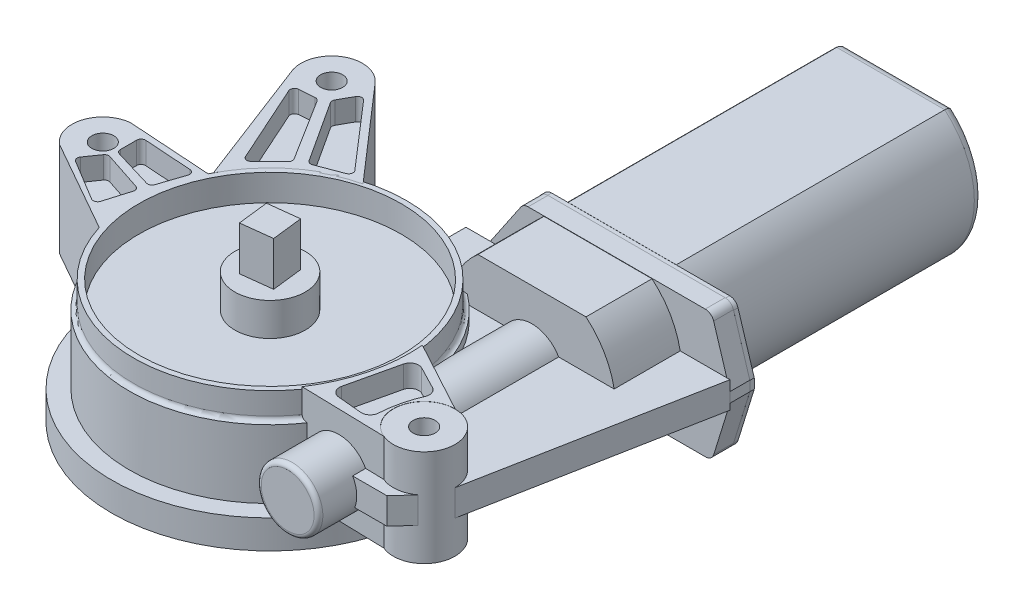
SolidWorks part; units mm, degrees
ref_plane "Спереди" through (0, 0, 0) normal (0, 0, 1) x (1, 0, 0)
ref_plane "Сверху" through (0, 0, 0) normal (0, 1, 0) x (1, 0, 0)
ref_plane "Справа" through (0, 0, 0) normal (1, 0, 0) x (0, 0, -1)
sketch "Эскиз3" plane through (0, 0, 0) normal (0, 0, 1) x (1, 0, 0)
  line L0 (0, 0) -> (56.6194, 0) construction
  line L1 (-12.278, 14.5) -> (12.278, 14.5)
  line L2 (-12.278, -14.5) -> (12.278, -14.5)
  arc A0 (-12.278, 14.5) -> (-12.278, -14.5) centre (0, 0) ccw
  arc A1 (12.278, -14.5) -> (12.278, 14.5) centre (0, 0) ccw
  dimension "D1" = 14.5
extrude "Вытянуть1" add sketch "Эскиз3" along normal blind 63
sketch "Эскиз4" plane through (0, 0, 0) normal (0, 0, -1) x (-1, 0, 0)
  circle A0 centre (0, 0) radius 6.75
extrude "Вытянуть2" add sketch "Эскиз4" along normal blind 5
sketch "Эскиз5" plane through (0, 0, -5) normal (0, 0, -1) x (-1, 0, 0)
  circle A0 centre (0, 0) radius 2.5
extrude "Вытянуть3" add sketch "Эскиз5" along normal blind 2 draft 33
sketch "Эскиз7" plane through (0, 0, 63) normal (0, 0, 1) x (1, 0, 0)
  line L0 (-29.9997, -12.4725) -> (-29.9997, -5.3043)
  line L1 (29.9997, -1.118) -> (26.3061, -13.0633)
  line L2 (-17.7001, 13.5889) -> (-29.6591, -4.1879)
  line L3 (29.9997, -1.118) -> (29.9997, 1.118)
  line L4 (24.3954, 14.4725) -> (-16.0407, 14.4725)
  line L5 (29.9997, 1.118) -> (26.3061, 13.0633)
  line L6 (24.3954, -14.4725) -> (-27.9997, -14.4725)
  line L7 (-29.9997, 0) -> (-36.554, 0) construction
  line L10 (0, 0) -> (0, 25.9429) construction
  arc A0 (-27.9997, -14.4725) -> (-29.9997, -12.4725) centre (-27.9997, -12.4725) cw
  arc A1 (-29.6591, -4.1879) -> (-29.9997, -5.3043) centre (-27.9997, -5.3043) ccw
  arc A5 (24.3954, -14.4725) -> (26.3061, -13.0633) centre (24.3954, -12.4725) ccw
  arc A6 (24.3954, 14.4725) -> (26.3061, 13.0633) centre (24.3954, 12.4725) cw
  arc A7 (-17.7001, 13.5889) -> (-16.0407, 14.4725) centre (-16.0407, 12.4725) cw
  point P0 (0, 0)
extrude "Вытянуть4" add sketch "Эскиз7" along normal blind 1
ref_plane "Плоскость1" through (0, -16.5, 0) normal (0, -1, 0) x (1, 0, 0)
sketch "Эскиз8" plane through (0, -16.5, 0) normal (0, -1, 0) x (1, 0, 0)
  line L0 (0, 0) -> (0, 81.1276) construction
  line L1 (23.2237, 64) -> (84.0137, 64) construction
  circle A1 centre (-34, 109) radius 36
extrude "Вытянуть5" add sketch "Эскиз8" against normal blind 6.5 separate body
sketch "Эскиз10" plane through (0, -10, 0) normal (0, -1, 0) x (-1, 0, 0)
  line L0 (0, 0) -> (0, 13.3727) construction
  circle A1 centre (34, -109) radius 32
extrude "Вытянуть6" add sketch "Эскиз10" against normal blind 15.5
sketch "Эскиз11" plane through (0, 5.5, 0) normal (0, 1, 0) x (1, 0, 0)
  line L0 (0, 0) -> (0, -27.8136) construction
  circle A2 centre (-34, -109) radius 29.8
  circle A3 centre (-34, -109) radius 31
extrude "Вытянуть7" add sketch "Эскиз11" along normal blind 6
fillet "Скругление1" radius 1 1 edges at (-34, 5.5, 78)
sketch "Эскиз12" plane through (0, -16.5, 0) normal (0, 1, 0) x (-1, 0, 0)
  line L0 (0, 0) -> (0, 26.2402) construction
  line L1 (65.6508, 115.1062) -> (55.1135, 133.3573)
  line L20 (51.6523, 133.3622) -> (41.0102, 115.0506)
  line L21 (63.9244, 112.1062) -> (42.7451, 112.0457)
  line L22 (55.1135, 84.6427) -> (65.6508, 102.8938)
  line L23 (63.9244, 105.8938) -> (42.7451, 105.9543)
  line L24 (51.6523, 84.6378) -> (41.0102, 102.9494)
  line L25 (23.4628, 78.5365) -> (44.5372, 78.5365)
  line L26 (46.2722, 81.5316) -> (35.7349, 99.9037)
  line L27 (21.7278, 81.5316) -> (32.2651, 99.9037)
  line L28 (2.3492, 102.8938) -> (12.8865, 84.6427)
  line L29 (16.3477, 84.6378) -> (26.9898, 102.9494)
  line L30 (4.0756, 105.8938) -> (25.2549, 105.9543)
  line L31 (12.8865, 133.3573) -> (2.3492, 115.1062)
  line L32 (4.0756, 112.1062) -> (25.2549, 112.0457)
  line L33 (16.3477, 133.3622) -> (26.9898, 115.0506)
  line L34 (46.2722, 136.4684) -> (35.7349, 118.0963)
  line L35 (21.7278, 136.4684) -> (32.2651, 118.0963)
  line L36 (44.5372, 139.4635) -> (23.4628, 139.4635)
  arc A18 (63.9244, 112.1062) -> (65.6508, 115.1062) centre (63.9187, 114.1062) ccw
  arc A19 (55.1135, 133.3573) -> (51.6523, 133.3622) centre (53.3815, 132.3573) ccw
  arc A20 (41.0102, 115.0506) -> (42.7451, 112.0457) centre (42.7394, 114.0457) ccw
  arc A21 (51.6523, 84.6378) -> (55.1135, 84.6427) centre (53.3815, 85.6427) ccw
  arc A22 (65.6508, 102.8938) -> (63.9244, 105.8938) centre (63.9187, 103.8938) ccw
  arc A23 (42.7451, 105.9543) -> (41.0102, 102.9494) centre (42.7394, 103.9543) ccw
  arc A24 (21.7278, 81.5316) -> (23.4628, 78.5365) centre (23.4628, 80.5365) ccw
  arc A25 (44.5372, 78.5365) -> (46.2722, 81.5316) centre (44.5372, 80.5365) ccw
  arc A26 (35.7349, 99.9037) -> (32.2651, 99.9037) centre (34, 98.9086) ccw
  arc A27 (4.0756, 105.8938) -> (2.3492, 102.8938) centre (4.0813, 103.8938) ccw
  arc A28 (12.8865, 84.6427) -> (16.3477, 84.6378) centre (14.6185, 85.6427) ccw
  arc A29 (26.9898, 102.9494) -> (25.2549, 105.9543) centre (25.2606, 103.9543) ccw
  arc A30 (16.3477, 133.3622) -> (12.8865, 133.3573) centre (14.6185, 132.3573) ccw
  arc A31 (2.3492, 115.1062) -> (4.0756, 112.1062) centre (4.0813, 114.1062) ccw
  arc A32 (25.2549, 112.0457) -> (26.9898, 115.0506) centre (25.2606, 114.0457) ccw
  arc A33 (32.2651, 118.0963) -> (35.7349, 118.0963) centre (34, 119.0914) ccw
  arc A34 (46.2722, 136.4684) -> (44.5372, 139.4635) centre (44.5372, 137.4635) ccw
  arc A35 (23.4628, 139.4635) -> (21.7278, 136.4684) centre (23.4628, 137.4635) ccw
  point P113 (34, 115.0714)
  point P114 (47.9899, 139.4635)
  point P115 (20.0101, 139.4635)
extrude "Вытянуть8" cut sketch "Эскиз12" along normal blind 1.2
sketch "Эскиз13" plane through (0, 5.5, 0) normal (0, 1, 0) x (1, 0, 0)
  line L0 (0, 0) -> (0, 38.3637) construction
  circle A1 centre (-34, -109) radius 8
extrude "Вытянуть9" add sketch "Эскиз13" along normal blind 7.5
sketch "Эскиз14" plane through (0, 13, 0) normal (0, 1, 0) x (1, 0, 0)
  line L0 (0, 0) -> (0, 36.0336) construction
  line L5 (-37.8867, -105.9351) -> (-30.9351, -105.1133)
  line L6 (-37.0649, -112.8867) -> (-37.8867, -105.9351)
  line L7 (-30.1133, -112.0649) -> (-37.0649, -112.8867)
  line L8 (-30.9351, -105.1133) -> (-30.1133, -112.0649)
  circle A1 centre (-34, -109) radius 3.5 construction
extrude "Вытянуть10" add sketch "Эскиз14" along normal blind 10
sketch "Эскиз15" plane through (0, 0, 64) normal (0, 0, 1) x (1, 0, 0)
  circle A0 centre (0, 0) radius 7
extrude "Вытянуть11" add sketch "Эскиз15" along normal blind 75
sketch "Эскиз16" plane through (0, 0, 64) normal (0, 0, 1) x (1, 0, 0)
  line L0 (12.278, 14.5) -> (-12.278, 14.5)
  line L1 (12.278, 14.5) -> (-12.278, 14.5) construction
  line L2 (12.278, -14.5) -> (-12.278, -14.5)
  arc A0 (-12.278, 14.5) -> (-12.278, -14.5) centre (0, 0) ccw
  arc A1 (12.278, -14.5) -> (12.278, 14.5) centre (0, 0) ccw
extrude "Вытянуть12" add sketch "Эскиз16" along normal blind 19.5
sketch "Эскиз17" plane through (0, 0, 64) normal (0, 0, 1) x (1, 0, 0)
  line L0 (-30.0005, -5.2705) -> (-30.0005, -12.4733)
  line L1 (29.9899, -1.1315) -> (26.3061, -13.0633)
  line L2 (24.361, 14.5741) -> (-15.8793, 14.5741)
  line L3 (29.9899, 1.1498) -> (29.9899, -1.1315)
  line L4 (-29.6549, -4.1467) -> (-17.5338, 13.6979)
  line L5 (0, 0) -> (0, 28.4439) construction
  line L6 (26.2716, 13.1654) -> (29.9899, 1.1498)
  line L7 (24.3951, -14.4733) -> (-28.0005, -14.4733)
  arc A0 (-28.0005, -14.4733) -> (-30.0005, -12.4733) centre (-28.0005, -12.4733) cw
  arc A1 (-29.6549, -4.1467) -> (-30.0005, -5.2705) centre (-28.0005, -5.2705) ccw
  arc A6 (26.3061, -13.0633) -> (24.3951, -14.4733) centre (24.3951, -12.4733) cw
  arc A7 (26.2716, 13.1654) -> (24.361, 14.5741) centre (24.361, 12.5741) ccw
  arc A8 (-15.8793, 14.5741) -> (-17.5338, 13.6979) centre (-15.8793, 12.5741) ccw
extrude "Вытянуть13" add sketch "Эскиз17" along normal blind 4.5
fillet "Скругление2" radius 1 1 edges at (7, 0, 139)
ref_plane "Плоскость2" through (0, -2.5, 0) normal (0, -1, 0) x (1, 0, 0)
ref_plane "Плоскость3" through (0, -10, 0) normal (0, 1, 0) x (-1, 0, 0)
sketch "Эскиз19" plane through (0, -10, 0) normal (0, 1, 0) x (-1, 0, 0)
  line L2 (0, 0) -> (0, -45.8668) construction
  circle A2 centre (-13, 121) radius 2.5
  circle A3 centre (-13, 121) radius 7
extrude "Вытянуть16" add sketch "Эскиз19" along normal blind 22
sketch "Эскиз18" plane through (0, -2.5, 0) normal (0, -1, 0) x (1, 0, 0)
  line L0 (-30.0005, 68.5) -> (29.9899, 68.5)
  line L1 (-2.1987, 112.5605) -> (-2.1987, 130.3043)
  line L2 (-2.1987, 130.3043) -> (13.853, 130.3043)
  line L3 (17.229, 126.5781) -> (13.853, 130.3043)
  line L4 (-30.0005, 77.2509) -> (-30.0005, 68.5)
  line L5 (29.9899, 68.5) -> (20, 121)
  line L6 (0, 0) -> (0, -15.0039) construction
  arc A1 (20, 121) -> (17.229, 126.5781) centre (13, 121) cw
  arc A3 (-30.0005, 77.2509) -> (-2.1987, 112.5605) centre (-34, 109) ccw
extrude "Вытянуть15" add sketch "Эскиз18" against normal blind 6
sketch "Эскиз20" plane through (0, -10, 0) normal (0, 1, 0) x (-1, 0, 0)
  line L2 (0, 0) -> (0, 43.7341) construction
  line L3 (-10.2818, 127.4507) -> (8.7473, 126.9805)
  line L4 (-13.0336, 113.982) -> (3.2391, 105.157)
  arc A9 (-13.0336, 113.982) -> (-10.2818, 127.4507) centre (-12.9558, 120.9816) ccw
  arc A10 (3.2391, 105.157) -> (8.7473, 126.9805) centre (37.2063, 108.1908) cw
extrude "Вытянуть21" add sketch "Эскиз20" along normal blind 22 separate body
sketch "Эскиз21" plane through (0, 12, 0) normal (0, 1, 0) x (1, 0, 0)
  line L3 (0, 0) -> (0, 31.3892) construction
  line L4 (-2.554, -124.8655) -> (2.9539, -125.3725)
  line L5 (-1.6954, -111.0431) -> (-4.3195, -122.4246)
  line L6 (6.2428, -112.3443) -> (1.1739, -109.7169)
  arc A5 (5.1338, -123.4968) -> (2.9539, -125.3725) centre (3.1372, -123.381) cw
  arc A6 (-2.554, -124.8655) -> (-4.3195, -122.4246) centre (-2.3706, -122.874) cw
  arc A7 (-1.6954, -111.0431) -> (1.1739, -109.7169) centre (0.2535, -111.4925) cw
  arc A8 (6.2428, -112.3443) -> (7.1603, -114.9089) centre (5.3224, -114.12) cw
  arc A9 (7.1603, -114.9089) -> (5.1338, -123.4968) centre (30.6107, -124.9754) ccw
extrude "Вытянуть23" cut sketch "Эскиз21" against normal blind 5
sketch "Эскиз22" plane through (0, -10, 0) normal (0, -1, 0) x (1, 0, 0)
  line L3 (0, 0) -> (0, 45.5523) construction
  line L4 (1.2936, 110.1573) -> (6.317, 112.4722)
  line L5 (-4.874, 122.5572) -> (-1.4559, 111.3884)
  line L6 (2.6512, 125.3994) -> (-3.0523, 125.1404)
  arc A5 (7.267, 115.1865) -> (6.317, 112.4722) centre (5.48, 114.2886) cw
  arc A6 (1.2936, 110.1573) -> (-1.4559, 111.3884) centre (0.4566, 111.9737) cw
  arc A7 (-4.874, 122.5572) -> (-3.0523, 125.1404) centre (-2.9616, 123.1425) cw
  arc A8 (2.6512, 125.3994) -> (4.728, 123.6372) centre (2.742, 123.4015) cw
  arc A9 (4.728, 123.6372) -> (7.267, 115.1865) centre (30.0699, 126.6445) ccw
extrude "Вытянуть24" cut sketch "Эскиз22" against normal blind 5
sketch "Эскиз23" plane through (0, -10, 0) normal (0, 1, 0) x (-1, 0, 0)
  line L0 (0, 0) -> (0, -17.6371) construction
  line L1 (72.3707, 65.9008) -> (61.3848, 94.4717)
  line L4 (60.6873, 58.442) -> (42.1989, 79.6831)
  arc A3 (42.1989, 79.6831) -> (61.3848, 94.4717) centre (35.4039, 108.3383) ccw
  circle A4 centre (66, 63) radius 2.5
  arc A6 (72.3707, 65.9008) -> (60.6873, 58.442) centre (66, 63) cw
extrude "Вытянуть27" add sketch "Эскиз23" along normal up to surface (21.5 mm away) separate body up to face at (-34, 11.5, 78)
sketch "Эскиз24" plane through (0, -10, 0) normal (0, 1, 0) x (1, 0, 0)
  line L0 (0, 0) -> (0, -33.9234) construction
  line L9 (-60.9369, -87.6399) -> (-68.9832, -69.7666)
  line L10 (-68.1428, -68.3587) -> (-64.6571, -68.1089)
  line L11 (-63.7383, -68.5752) -> (-54.9646, -82.5698)
  line L12 (-55.112, -83.8152) -> (-59.3252, -87.9437)
  line L13 (-51.701, -81.6376) -> (-46.1827, -79.5534)
  line L14 (-61.8946, -67.3981) -> (-52.8928, -81.2471)
  line L15 (-60.2372, -63.3116) -> (-61.9309, -66.3685)
  line L16 (-45.7799, -77.9636) -> (-58.6063, -63.1419)
  arc A9 (-68.1428, -68.3587) -> (-68.9832, -69.7666) centre (-68.0714, -69.3561) ccw
  arc A10 (-63.7383, -68.5752) -> (-64.6571, -68.1089) centre (-64.5856, -69.1064) ccw
  arc A11 (-55.112, -83.8152) -> (-54.9646, -82.5698) centre (-55.8119, -83.1009) ccw
  arc A12 (-60.9369, -87.6399) -> (-59.3252, -87.9437) centre (-60.0251, -87.2294) ccw
  arc A13 (-45.7799, -77.9636) -> (-46.1827, -79.5534) centre (-46.5361, -78.6179) cw
  arc A14 (-51.701, -81.6376) -> (-52.8928, -81.2471) centre (-52.0543, -80.7021) cw
  arc A15 (-61.8946, -67.3981) -> (-61.9309, -66.3685) centre (-61.0562, -66.8531) cw
  arc A16 (-60.2372, -63.3116) -> (-58.6063, -63.1419) centre (-59.3625, -63.7963) cw
extrude "Вытянуть28" cut sketch "Эскиз24" along normal blind 5
sketch "Эскиз25" plane through (0, 11.5, 0) normal (0, -1, 0) x (1, 0, 0)
  line L4 (0, 0) -> (0, 34.4107) construction
  line L9 (-68.9832, 69.7666) -> (-60.9369, 87.6399)
  line L10 (-64.6571, 68.1089) -> (-68.1428, 68.3587)
  line L11 (-54.9646, 82.5698) -> (-63.7383, 68.5752)
  line L12 (-59.3252, 87.9437) -> (-55.112, 83.8152)
  line L13 (-58.6063, 63.1419) -> (-45.7799, 77.9636)
  line L14 (-61.9309, 66.3685) -> (-60.2372, 63.3116)
  line L15 (-52.8928, 81.2471) -> (-61.8946, 67.3981)
  line L16 (-46.1827, 79.5534) -> (-51.701, 81.6376)
  arc A8 (-60.9369, 87.6399) -> (-59.3252, 87.9437) centre (-60.0251, 87.2294) cw
  arc A9 (-68.1428, 68.3587) -> (-68.9832, 69.7666) centre (-68.0714, 69.3561) cw
  arc A10 (-64.6571, 68.1089) -> (-63.7383, 68.5752) centre (-64.5856, 69.1064) ccw
  arc A11 (-45.7799, 77.9636) -> (-46.1827, 79.5534) centre (-46.5361, 78.6179) ccw
  arc A12 (-51.701, 81.6376) -> (-52.8928, 81.2471) centre (-52.0543, 80.7021) ccw
  arc A13 (-61.9309, 66.3685) -> (-61.8946, 67.3981) centre (-61.0562, 66.8531) cw
  arc A14 (-60.2372, 63.3116) -> (-58.6063, 63.1419) centre (-59.3625, 63.7963) ccw
  arc A15 (-55.112, 83.8152) -> (-54.9646, 82.5698) centre (-55.8119, 83.1009) cw
extrude "Вытянуть29" cut sketch "Эскиз25" along normal blind 5
sketch "Эскиз26" plane through (0, -10, 0) normal (0, 1, 0) x (-1, 0, 0)
  line L0 (-27.2099, 64) -> (-121.7072, 64) construction
  line L1 (0, 0) -> (0, 18.5901) construction
  line L4 (84.5472, 106.3219) -> (63.6005, 118.2094)
  line L5 (80.6673, 94.0319) -> (61.7986, 95.2801)
  arc A4 (61.7986, 95.2801) -> (63.6005, 118.2094) centre (34, 109) ccw
  circle A5 centre (80, 101) radius 2.5
  arc A6 (84.5472, 106.3219) -> (80.6673, 94.0319) centre (80, 101) cw
extrude "Вытянуть30" add sketch "Эскиз26" along normal up to surface (21.5 mm away) up to face at (-34, 11.5, 78)
sketch "Эскиз27" plane through (0, -10, 0) normal (0, -1, 0) x (-1, 0, 0)
  line L0 (63.8177, -97.8045) -> (65.7058, -103.4687)
  line L1 (66.9436, -104.1098) -> (75.8239, -101.4281)
  line L2 (76.5348, -100.4708) -> (76.5348, -96.7619)
  line L3 (75.4675, -95.7641) -> (64.6991, -96.4906)
  line L4 (67.5247, -105.9505) -> (76.3351, -103.0473)
  line L5 (77.4668, -103.4229) -> (79.5963, -106.4595)
  line L6 (79.2954, -107.8892) -> (70.0618, -113.4773)
  line L7 (68.5858, -112.9076) -> (66.8794, -107.1861)
  line L9 (0, 0) -> (0, 14.9937) construction
  arc A1 (76.5348, -96.7619) -> (75.4675, -95.7641) centre (75.5348, -96.7619) ccw
  arc A2 (75.8239, -101.4281) -> (76.5348, -100.4708) centre (75.5348, -100.4708) ccw
  arc A3 (65.7058, -103.4687) -> (66.9436, -104.1098) centre (66.6545, -103.1525) ccw
  arc A4 (64.6991, -96.4906) -> (63.8177, -97.8045) centre (64.7664, -97.4883) ccw
  arc A5 (76.3351, -103.0473) -> (77.4668, -103.4229) centre (76.6481, -103.9971) cw
  arc A6 (79.5963, -106.4595) -> (79.2954, -107.8892) centre (78.7776, -107.0337) cw
  arc A7 (70.0618, -113.4773) -> (68.5858, -112.9076) centre (69.544, -112.6218) cw
  arc A8 (66.8794, -107.1861) -> (67.5247, -105.9505) centre (67.8377, -106.9003) cw
sketch "Эскиз28" plane through (0, 11.5, 0) normal (0, -1, 0) x (1, 0, 0)
  line L0 (0, 0) -> (0, 24.8324) construction
  line L10 (-66.8794, 107.1861) -> (-68.5858, 112.9076)
  line L11 (-76.3351, 103.0473) -> (-67.5247, 105.9505)
  line L12 (-79.5963, 106.4595) -> (-77.4668, 103.4229)
  line L13 (-70.0618, 113.4773) -> (-79.2954, 107.8892)
  line L14 (-75.8239, 101.4281) -> (-66.9436, 104.1098)
  line L15 (-76.5348, 96.7619) -> (-76.5348, 100.4708)
  line L16 (-64.6991, 96.4906) -> (-75.4675, 95.7641)
  line L17 (-65.7058, 103.4687) -> (-63.8177, 97.8045)
  arc A8 (-67.5247, 105.9505) -> (-66.8794, 107.1861) centre (-67.8377, 106.9003) ccw
  arc A9 (-77.4668, 103.4229) -> (-76.3351, 103.0473) centre (-76.6481, 103.9971) ccw
  arc A10 (-79.2954, 107.8892) -> (-79.5963, 106.4595) centre (-78.7776, 107.0337) ccw
  arc A11 (-68.5858, 112.9076) -> (-70.0618, 113.4773) centre (-69.544, 112.6218) ccw
  arc A12 (-63.8177, 97.8045) -> (-64.6991, 96.4906) centre (-64.7664, 97.4883) cw
  arc A13 (-75.4675, 95.7641) -> (-76.5348, 96.7619) centre (-75.5348, 96.7619) cw
  arc A14 (-76.5348, 100.4708) -> (-75.8239, 101.4281) centre (-75.5348, 100.4708) cw
  arc A15 (-66.9436, 104.1098) -> (-65.7058, 103.4687) centre (-66.6545, 103.1525) cw
extrude "Вытянуть31" cut sketch "Эскиз27" against normal blind 5
extrude "Вытянуть32" cut sketch "Эскиз28" along normal blind 5
fillet "Скругление3" radius 2 4 edges at (0, 14.5, 0) (0, -14.5, 0) (-19, 0, 0) (19, 0, 0)
fillet "Скругление4" radius 1 1 edges at (-6.75, 0, -5)
fillet "Скругление5" radius 0.5 1 edges at (-1.2012, 0, -7)
